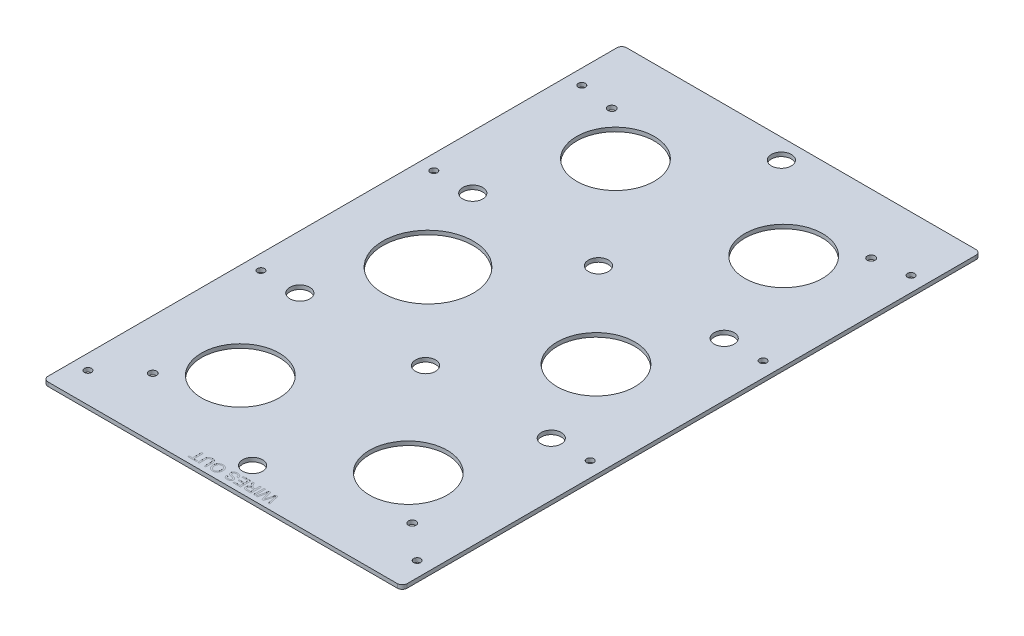
SolidWorks part; units mm, degrees
ref_plane "Front" through (0, 0, 0) normal (0, 0, 1) x (1, 0, 0)
ref_plane "Top" through (0, 0, 0) normal (0, 1, 0) x (1, 0, 0)
ref_plane "Right" through (0, 0, 0) normal (1, 0, 0) x (0, 0, -1)
sketch "Sketch1" plane through (0, 0, 0) normal (0, 1, 0) x (1, 0, 0)
  line L0 (480.5613, -418.2689) -> (480.4343, -418.2689) construction
  line L1 (447.5541, -114.7389) -> (669.8041, -114.7389)
  line L2 (444.3791, -117.9139) -> (444.3791, -479.8639)
  line L3 (447.5541, -483.0389) -> (669.8041, -483.0389)
  line L4 (672.9791, -117.9139) -> (672.9791, -479.8639)
  line L5 (444.3791, -114.7389) -> (672.9791, -483.0389) construction
  line L6 (444.3791, -483.0389) -> (672.9791, -114.7389) construction
  line L7 (485.5654, -278.8246) -> (524.7572, -318.8246) construction
  line L8 (585.6666, -483.0389) -> (669.8041, -483.0389) construction
  line L9 (672.9791, -479.8639) -> (672.9791, -117.9139) construction
  circle A0 centre (612.1969, -418.3975) radius 24.727
  circle A1 centre (612.1969, -298.9532) radius 24.727
  circle A2 centre (505.1613, -418.2689) radius 24.727
  circle A4 centre (505.1613, -179.5089) radius 24.727
  circle A5 centre (612.1969, -179.5089) radius 24.727
  arc A6 (510.1181, -442.3644) -> (507.7696, -393.8076) centre (505.1613, -418.2689) ccw construction
  arc A7 (510.1181, -442.3644) -> (500.2045, -394.1735) centre (505.1613, -418.2689) ccw construction
  arc A8 (672.9791, -117.9139) -> (669.8041, -114.7389) centre (669.8041, -117.9139) ccw
  arc A9 (444.3791, -117.9139) -> (447.5541, -114.7389) centre (447.5541, -117.9139) cw
  arc A10 (444.3791, -479.8639) -> (447.5541, -483.0389) centre (447.5541, -479.8639) ccw
  arc A11 (669.8041, -483.0389) -> (672.9791, -479.8639) centre (669.8041, -479.8639) ccw
  circle A12 centre (505.1613, -298.8246) radius 28.7693
  circle A13 centre (478.6691, -353.918) radius 2.2479 construction
  circle A14 centre (478.6691, -353.918) radius 2.2479 construction
  circle A15 centre (558.6791, -353.9222) radius 2.2479 construction
  circle A16 centre (558.6791, -353.9222) radius 2.2479 construction
  circle A17 centre (638.6891, -353.918) radius 2.2479 construction
  circle A18 centre (638.6891, -353.918) radius 2.2479 construction
  circle A19 centre (638.6891, -243.8598) radius 2.2479 construction
  circle A20 centre (638.6891, -243.8598) radius 2.2479 construction
  circle A21 centre (558.6791, -243.8556) radius 2.2479 construction
  circle A22 centre (558.6791, -243.8556) radius 2.2479 construction
  circle A23 centre (478.6691, -243.8598) radius 2.2479 construction
  circle A24 centre (478.6691, -243.8598) radius 2.2479 construction
  circle A25 centre (558.6791, -127.4389) radius 2.2479 construction
  circle A26 centre (558.6791, -127.4389) radius 2.2479 construction
  circle A27 centre (558.6791, -463.9889) radius 2.2479 construction
  circle A28 centre (558.6791, -463.9889) radius 2.2479 construction
  circle A29 centre (558.6791, -463.9889) radius 6.35
  circle A30 centre (638.6891, -353.918) radius 6.35
  circle A31 centre (558.6791, -353.9222) radius 6.35
  circle A32 centre (478.6691, -353.918) radius 6.35
  circle A33 centre (638.6891, -243.8598) radius 6.35
  circle A34 centre (558.6791, -243.8556) radius 6.35
  circle A35 centre (478.6691, -243.8598) radius 6.35
  circle A36 centre (558.6791, -127.4389) radius 6.35
  circle A37 centre (641.2291, -152.8389) radius 2.4574 construction
  circle A38 centre (641.2291, -152.8389) radius 2.4575
  circle A39 centre (476.1291, -152.8389) radius 2.4574 construction
  circle A40 centre (476.1291, -152.8389) radius 2.4575
  circle A41 centre (476.1291, -444.9389) radius 2.4574 construction
  circle A42 centre (476.1291, -444.9389) radius 2.4575
  circle A43 centre (641.2291, -444.9389) radius 2.4575 construction
  circle A44 centre (641.2291, -444.9389) radius 2.4575
  circle A45 centre (453.9041, -149.6639) radius 2.2479 construction
  circle A46 centre (453.9041, -149.6639) radius 2.2479
  circle A47 centre (453.9041, -243.8556) radius 2.2479 construction
  circle A48 centre (453.9041, -243.8556) radius 2.2479
  circle A49 centre (663.4541, -149.6639) radius 2.2479 construction
  circle A50 centre (663.4541, -149.6639) radius 2.2479
  circle A51 centre (663.4541, -243.8556) radius 2.2479 construction
  circle A52 centre (663.4541, -243.8556) radius 2.2479
  circle A53 centre (663.4541, -353.9222) radius 2.2479 construction
  circle A54 centre (663.4541, -353.9222) radius 2.2479
  circle A55 centre (453.9041, -353.9222) radius 2.2479 construction
  circle A56 centre (453.9041, -353.9222) radius 2.2479
  circle A57 centre (453.9041, -463.9889) radius 2.2479 construction
  circle A58 centre (453.9041, -463.9889) radius 2.2479
  circle A59 centre (663.4541, -463.9889) radius 2.2479 construction
  circle A60 centre (663.4541, -463.9889) radius 2.2479
  point P0 (558.6791, -298.8889)
  dimension "D3" = 0.127
  dimension "D4" = 3.175
  dimension "D5" = 12.7
  dimension "D1" = 228.6
  dimension "D2" = 368.3
extrude "Boss-Extrude1" add sketch "Sketch1" along normal blind 2.54
sketch "Sketch2" plane through (0, 2.54, 0) normal (0, 1, 0) x (1, 0, 0)
  line L0 (585.4717, -473.0389) -> (585.4717, -483.0389) construction
  line L2 (585.4717, -473.0389) -> (534.6717, -473.0389) construction
  line L3 (447.5541, -483.0389) -> (669.8041, -483.0389) construction
  line L4 (672.9791, -479.8639) -> (672.9791, -117.9139) construction
  text T0 "WIRES OUT" font "Arial" height in points 26
  dimension "D1" = 10
  dimension "D2" = 50.8
  dimension "D3" = 87.5074
extrude "Cut-Extrude2" cut sketch "Sketch2" against normal blind 0.0254
